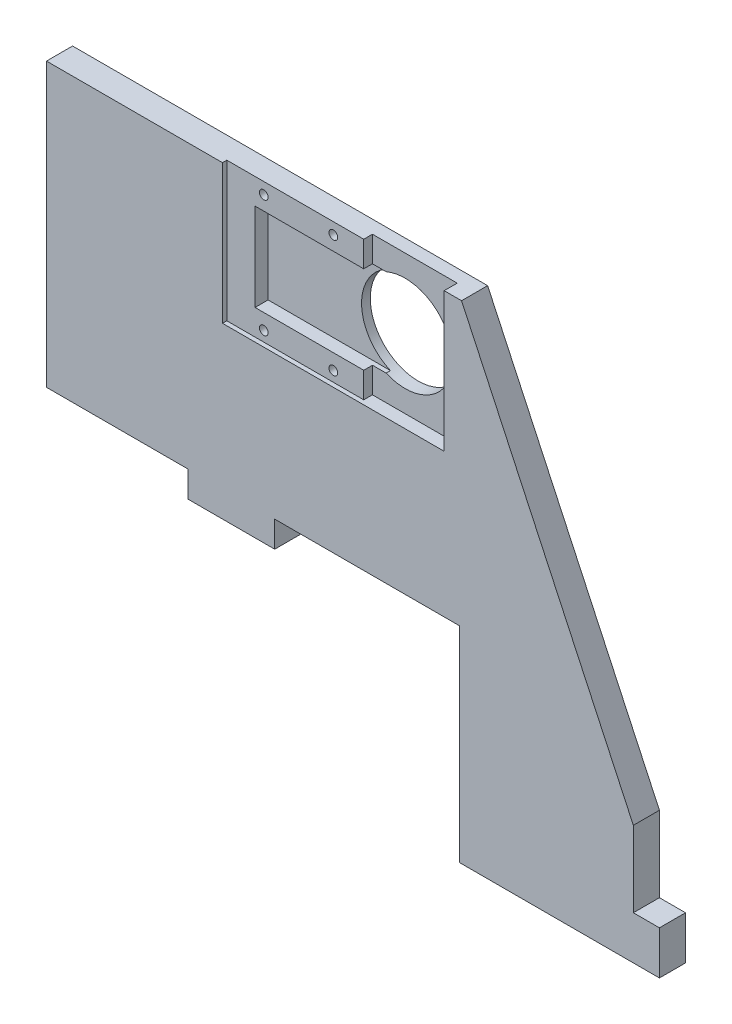
SolidWorks part; units mm, degrees
ref_plane "Plan de face" through (0, 0, 0) normal (0, 0, 1) x (1, 0, 0)
ref_plane "Plan de dessus" through (0, 0, 0) normal (0, 1, 0) x (1, 0, 0)
ref_plane "Plan de droite" through (0, 0, 0) normal (1, 0, 0) x (0, 0, -1)
sketch "Esquisse1" plane through (0, 0, 0) normal (0, 0, 1) x (1, 0, 0)
  line L1 (-67.5, 56.085) -> (67.5, 56.085)
  line L2 (-67.5, 56.085) -> (-67.5, -56.085)
  line L3 (-67.5, -56.085) -> (67.5, -56.085)
  line L4 (67.5, 56.085) -> (67.5, -56.085)
  dimension "D1" = 135
  dimension "D2" = 112.17
  dimension "D3" = 67.5
  dimension "D4" = 56.085
extrude "Boss.-Extru.1" add sketch "Esquisse1" along normal blind 6
sketch "Esquisse2" plane through (0, 0, 6) normal (0, 0, 1) x (1, 0, 0)
  line L0 (-67.5, -56.085) -> (67.5, -56.085) construction
  line L1 (27.5, -56.085) -> (-67.5, -56.085)
  line L2 (27.5, -56.085) -> (27.5, -8.915)
  line L3 (-38.5, -8.915) -> (27.5, -8.915)
  line L4 (-67.5, -56.085) -> (-67.5, -8.915)
  line L5 (-67.5, 56.085) -> (-67.5, -56.085) construction
  line L7 (67.5, -28.665) -> (27.9804, 56.085)
  line L8 (-38.5, -8.915) -> (-67.5, -8.915)
  line L9 (67.5, -56.085) -> (67.5, 56.085) construction
  line L10 (67.5, 56.085) -> (-67.5, 56.085) construction
  line L11 (27.9804, 56.085) -> (67.5, 56.085)
  line L12 (67.5, 56.085) -> (67.5, -28.665)
  dimension "D1" = 47.17
  dimension "D2" = 95
  dimension "D3" = 27.42
  dimension "D4" = 155
  dimension "D5" = 115
extrude "Enlèv. mat.-Extru.1" cut sketch "Esquisse2" against normal blind 6
sketch "Esquisse3" plane through (0, 0, 6) normal (0, 0, 1) x (1, 0, 0)
  line L0 (67.5, -56.085) -> (67.5, -28.665) construction
  line L1 (67.5, -56.085) -> (73.5, -56.085)
  line L2 (67.5, -56.085) -> (67.5, -46.085)
  line L3 (67.5, -46.085) -> (73.5, -46.085)
  line L4 (73.5, -56.085) -> (73.5, -46.085)
  line L6 (-35, -8.915) -> (-15, -8.915)
  line L7 (-35, -8.915) -> (-35, -14.915)
  line L8 (-35, -14.915) -> (-15, -14.915)
  line L9 (-15, -8.915) -> (-15, -14.915)
  line L10 (27.5, -8.915) -> (-67.5, -8.915) construction
  line L16 (27.5, -56.085) -> (27.5, -8.915) construction
  dimension "D3" = 6
  dimension "D4" = 20
  dimension "D5" = 42.5
  dimension "D6" = 10
  dimension "D7" = 6
extrude "Boss.-Extru.2" add sketch "Esquisse3" against normal blind 6
sketch "Esquisse4" plane through (0, 0, 6) normal (0, 0, 1) x (1, 0, 0)
  line L0 (27.9804, 56.085) -> (-67.5, 56.085) construction
  line L1 (-27.0196, 56.085) -> (23.9804, 56.085)
  line L2 (-27.0196, 56.085) -> (-27.0196, 24.085)
  line L3 (-27.0196, 24.085) -> (23.9804, 24.085)
  line L4 (23.9804, 56.085) -> (23.9804, 24.085)
  dimension "D1" = 51
  dimension "D2" = 32
  dimension "D3" = 4
  dimension "D4" = 0
extrude "Enlèv. mat.-Extru.2" cut sketch "Esquisse4" against normal blind 3
sketch "Esquisse5" plane through (0, 0, 3) normal (0, 0, 1) x (1, 0, 0)
  line L0 (23.9804, 24.085) -> (23.9804, 56.085) construction
  line L1 (23.9804, 56.085) -> (-27.0196, 56.085) construction
  circle A0 centre (11.9804, 40.085) radius 11
  point P2 (23.9804, 40.085)
  dimension "D1" = 22
  dimension "D2" = 12
  dimension "D3" = 16
extrude "Enlèv. mat.-Extru.3" cut sketch "Esquisse5" against normal through all
sketch "Esquisse6" plane through (0, 0, 3) normal (0, 0, 1) x (1, 0, 0)
  line L1 (-20.5196, 50.185) -> (9.4804, 50.185)
  line L2 (-20.5196, 50.185) -> (-20.5196, 29.985)
  line L3 (-20.5196, 29.985) -> (9.4804, 29.985)
  line L4 (9.4804, 50.185) -> (9.4804, 29.985)
  circle A0 centre (11.9804, 40.085) radius 11 construction
  dimension "D1" = 30
  dimension "D2" = 20.2
  dimension "D3" = 10.1
  dimension "D4" = 32.5
extrude "Enlèv. mat.-Extru.4" cut sketch "Esquisse6" against normal blind 1
sketch "Esquisse7" plane through (0, 0, 3) normal (0, 0, 1) x (1, 0, 0)
  line L0 (23.9804, 56.085) -> (-27.0196, 56.085) construction
  line L1 (4.4804, 56.085) -> (-20.5196, 56.085)
  line L2 (4.4804, 56.085) -> (4.4804, 50.185)
  line L3 (4.4804, 50.185) -> (-20.5196, 50.185)
  line L4 (-20.5196, 56.085) -> (-20.5196, 50.185)
  dimension "D1" = 25
extrude "Boss.-Extru.3" add sketch "Esquisse7" along normal blind 2
sketch "Esquisse8" plane through (0, 0, 3) normal (0, 0, 1) x (1, 0, 0)
  line L1 (-27.0196, 24.085) -> (23.9804, 24.085) construction
  line L2 (-20.5196, 29.985) -> (4.4804, 29.985)
  line L3 (-20.5196, 29.985) -> (-20.5196, 24.085)
  line L4 (-20.5196, 24.085) -> (4.4804, 24.085)
  line L5 (4.4804, 29.985) -> (4.4804, 24.085)
  dimension "D1" = 25
extrude "Boss.-Extru.4" add sketch "Esquisse8" along normal blind 2
sketch "Esquisse9" plane through (0, 0, 3) normal (0, 0, 1) x (1, 0, 0)
  line L1 (-27.0196, 56.085) -> (-20.5196, 56.085)
  line L2 (-27.0196, 56.085) -> (-27.0196, 24.085)
  line L3 (-27.0196, 24.085) -> (-20.5196, 24.085)
  line L4 (-20.5196, 56.085) -> (-20.5196, 24.085)
extrude "Boss.-Extru.5" add sketch "Esquisse9" along normal blind 2
sketch "Esquisse10" plane through (0, 0, 5) normal (0, 0, 1) x (1, 0, 0)
  line L0 (-27.0196, 56.085) -> (-27.0196, 24.085) construction
  line L1 (-27.0196, 56.085) -> (-27.0196, 24.085) construction
  line L4 (4.4804, 56.085) -> (-27.0196, 56.085) construction
  line L6 (-20.5196, 29.985) -> (7.6227, 29.985) construction
  circle A0 centre (-18.5196, 53.435) radius 1
  circle A1 centre (-2.5196, 53.435) radius 1
  circle A2 centre (-18.5196, 26.435) radius 1
  circle A3 centre (-2.5196, 26.435) radius 1
  dimension "D1" = 2
  dimension "D2" = 2
  dimension "D3" = 8.5
  dimension "D4" = 16
  dimension "D5" = 2
  dimension "D6" = 2
  dimension "D9" = 2.65
  dimension "D10" = 3.55
  dimension "D11" = 2.65
  dimension "D12" = 3.55
  dimension "D7" = 16
  dimension "D8" = 8.5
extrude "Enlèv. mat.-Extru.5" cut sketch "Esquisse10" against normal through all
equation "\"D3@Esquisse1\"=\"D1@Esquisse1\"/2"
equation "\"D4@Esquisse1\"=\"D2@Esquisse1\"/2"
